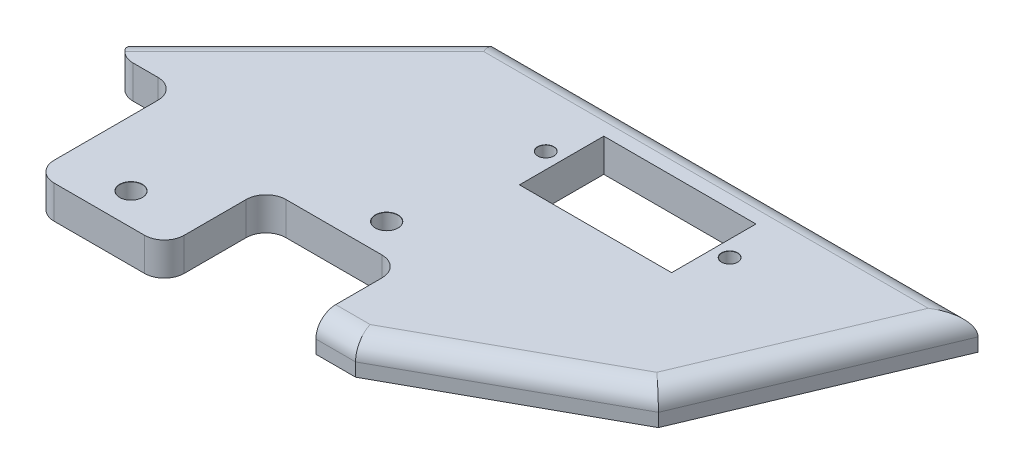
SolidWorks part; units mm, degrees
ref_plane "Front Plane" through (0, 0, 0) normal (0, 0, 1) x (1, 0, 0)
ref_plane "Top Plane" through (0, 0, 0) normal (0, 1, 0) x (1, 0, 0)
ref_plane "Right Plane" through (0, 0, 0) normal (1, 0, 0) x (0, 0, -1)
sketch "Sketch1" plane through (0, 0, 0) normal (0, 1, 0) x (1, 0, 0)
  line L0 (-6.83, 0) -> (6.83, 0)
  line L1 (9.83, 3) -> (9.83, 12.37)
  line L2 (12.83, 15.37) -> (27.36, 15.37)
  line L3 (30.36, 12.37) -> (30.36, 2.37)
  line L4 (30.36, 2.37) -> (36.36, 2.37)
  line L5 (-9.83, 3) -> (-9.83, 18.69)
  line L6 (-12.83, 21.69) -> (-23.83, 21.69)
  line L7 (-23.83, 21.69) -> (-23.83, 27.69)
  line L8 (-23.83, 27.69) -> (36.36, 27.69)
  line L9 (36.36, 27.69) -> (36.36, 2.37)
  arc A0 (27.36, 15.37) -> (30.36, 12.37) centre (27.36, 12.37) cw
  arc A1 (9.83, 12.37) -> (12.83, 15.37) centre (12.83, 12.37) cw
  arc A2 (6.83, 0) -> (9.83, 3) centre (6.83, 3) ccw
  arc A3 (-6.83, 0) -> (-9.83, 3) centre (-6.83, 3) cw
  arc A4 (-9.83, 18.69) -> (-12.83, 21.69) centre (-12.83, 18.69) ccw
  point P21 (0, 0)
  dimension "D1" = 3
  dimension "D2" = 13.66
  dimension "D3" = 15.69
  dimension "D4" = 9.37
  dimension "D5" = 14.53
  dimension "D6" = 10
  dimension "D7" = 6
  dimension "D8" = 11
  dimension "D9" = 6
extrude "Boss-Extrude1" add sketch "Sketch1" along normal blind 5
hole_wizard "M3 Clearance Hole1" positions "Sketch2" profile "Sketch3" hole size "M3" standard "ANSI Metric" end condition through all
sketch "Sketch2" plane through (0, 5, 0) normal (0, 1, 0) x (1, 0, 0)
  line L1 (0, 4.79) -> (0, 0) construction
  line L6 (20.095, 15.37) -> (20.095, 20.11) construction
  line L7 (12.83, 15.37) -> (27.36, 15.37) construction
  line L8 (20.095, 20.11) -> (23.325, 20.11) construction
  point P0 (0, 4.79)
  point P2 (23.325, 20.11)
  dimension "D1" = 4.79
  dimension "D2" = 4.74
  dimension "D3" = 3.23
sketch "Sketch3" plane through (0, 5, -4.79) normal (1, 0, 0) x (0, 0, 1)
  line L0 (0, 0) -> (0, 5)
  line L1 (0, 5) -> (1.7, 5)
  line L2 (1.7, 5) -> (1.7, 0.025)
  line L3 (1.7, 0.025) -> (1.725, 0)
  line L5 (1.725, 0) -> (0, 0)
  line L6 (-1.7, 0.025) -> (-1.725, 0) construction
  line L11 (0, -6.35) -> (0, 107.95) construction
  dimension "Thru Hole Dia." = 3.4
  dimension "Thru Hole Depth" = 5
  dimension "Near C'Sink Dia." = 3.45
  dimension "Near C'Sink Angle" = 90
sketch "Sketch4" plane through (0, 5, 0) normal (0, 1, 0) x (1, 0, 0)
  line L0 (0, 4.79) -> (40.07, 4.79) construction
  line L2 (40.07, 4.79) -> (80.14, 4.79) construction
  line L3 (-23.83, 27.69) -> (-23.83, 52.69)
  line L4 (-23.83, 52.69) -> (80.14, 52.69)
  line L5 (80.14, 52.69) -> (80.14, 4.79)
  line L6 (36.36, 27.69) -> (-23.83, 27.69) construction
  line L7 (36.36, 2.37) -> (36.36, 27.69) construction
  line L8 (36.36, 2.37) -> (36.36, 27.69)
  line L9 (36.36, 27.69) -> (-23.83, 27.69)
  line L11 (36.36, 2.37) -> (80.14, 2.37)
  line L12 (80.14, 2.37) -> (80.14, 4.79)
  circle A0 centre (0, 4.79) radius 1.725 construction
  circle A1 centre (0, 4.79) radius 1.725 construction
  point P8 (77.7905, 2.37)
  dimension "D1" = 40.07
  dimension "D2" = 25
extrude "Boss-Extrude2" add sketch "Sketch4" against normal up to surface (5 mm away) up to face at (0, 0, -3.09)
sketch "Sketch5" plane through (0, 5, 0) normal (0, 1, 0) x (1, 0, 0)
  line L0 (-23.83, 27.69) -> (80.14, 27.69) construction
  line L1 (-23.83, 52.69) -> (-23.83, 21.69) construction
  line L2 (80.14, 2.37) -> (80.14, 52.69) construction
  line L3 (-23.83, 21.69) -> (-12.83, 21.69) construction
  line L4 (0, 4.79) -> (40.07, 4.79) construction
  line L5 (80.14, 52.69) -> (-23.83, 52.69) construction
  line L6 (51.57, 47.69) -> (28.57, 47.69)
  line L7 (51.57, 47.69) -> (51.57, 34.94)
  line L8 (51.57, 34.94) -> (28.57, 34.94)
  line L9 (28.57, 47.69) -> (28.57, 34.94)
  line L10 (51.57, 47.69) -> (28.57, 34.94) construction
  line L11 (51.57, 34.94) -> (28.57, 47.69) construction
  circle A0 centre (0, 4.79) radius 1.725 construction
  circle A1 centre (0, 4.79) radius 1.725 construction
  point P11 (40.07, 41.315)
  point P17 (0, 0)
  dimension "D1" = 6
  dimension "D2" = 40.07
  dimension "D3" = 12.75
  dimension "D4" = 23
  dimension "D5" = 5
extrude "Cut-Extrude1" cut sketch "Sketch5" against normal up to surface (5 mm away) up to face at (13.4214, 0, -15.6194)
hole_wizard "M2 Clearance Hole1" positions "Sketch6" profile "Sketch7" hole size "M2" standard "ANSI Metric" end condition through all
sketch "Sketch6" plane through (0, 5, 0) normal (0, 1, 0) x (1, 0, 0)
  line L0 (51.57, 47.69) -> (28.57, 47.69) construction
  line L1 (51.57, 34.94) -> (51.57, 47.69) construction
  line L2 (51.57, 47.69) -> (28.57, 47.69) construction
  line L3 (51.57, 34.94) -> (51.57, 47.69) construction
  line L4 (26.17, 41.315) -> (53.97, 41.315) construction
  point P0 (26.17, 41.315)
  point P2 (53.97, 41.315)
  point P8 (51.57, 41.315)
  point P14 (40.07, 41.315)
  point P15 (40.07, 47.69)
  dimension "D1" = 27.8
sketch "Sketch7" plane through (26.17, 5, -41.315) normal (1, 0, 0) x (0, 0, 1)
  line L0 (0, 0) -> (0, 5)
  line L1 (0, 5) -> (1.2, 5)
  line L2 (1.2, 5) -> (1.2, 0.025)
  line L3 (1.2, 0.025) -> (1.225, 0)
  line L5 (1.225, 0) -> (0, 0)
  line L6 (-1.2, 0.025) -> (-1.225, 0) construction
  line L11 (0, -6.35) -> (0, 107.95) construction
  dimension "Thru Hole Dia." = 2.4
  dimension "Thru Hole Depth" = 5
  dimension "Near C'Sink Dia." = 2.45
  dimension "Near C'Sink Angle" = 90
sketch "Sketch8" plane through (0, 5, 0) normal (0, 1, 0) x (1, 0, 0)
  line L0 (51.57, 34.94) -> (80.14, 2.37) construction
  line L2 (65.855, 18.655) -> (80.14, 52.69)
  line L3 (-23.83, 21.69) -> (7.17, 52.69)
  line L4 (80.14, 52.69) -> (-23.83, 52.69) construction
  line L5 (7.17, 52.69) -> (-23.83, 52.69)
  line L6 (-23.83, 52.69) -> (-23.83, 21.69)
  line L8 (80.14, 2.37) -> (80.14, 52.69)
  line L9 (65.855, 18.655) -> (36.36, 2.37)
  line L10 (30.36, 2.37) -> (80.14, 2.37) construction
  line L11 (36.36, 2.37) -> (80.14, 2.37)
  dimension "D1" = 45
  dimension "D2" = 6
extrude "Cut-Extrude2" cut sketch "Sketch8" against normal up to surface (5 mm away) up to face at (26.17, 0, -40.115)
fillet "Fillet2" radius 3 6 edges at (-23.83, 2.5, -21.69) (-8.33, 5, -37.19) (43.655, 5, -52.69) (72.9975, 5, -35.6725) (51.1075, 5, -10.5125) (33.36, 5, -2.37)
